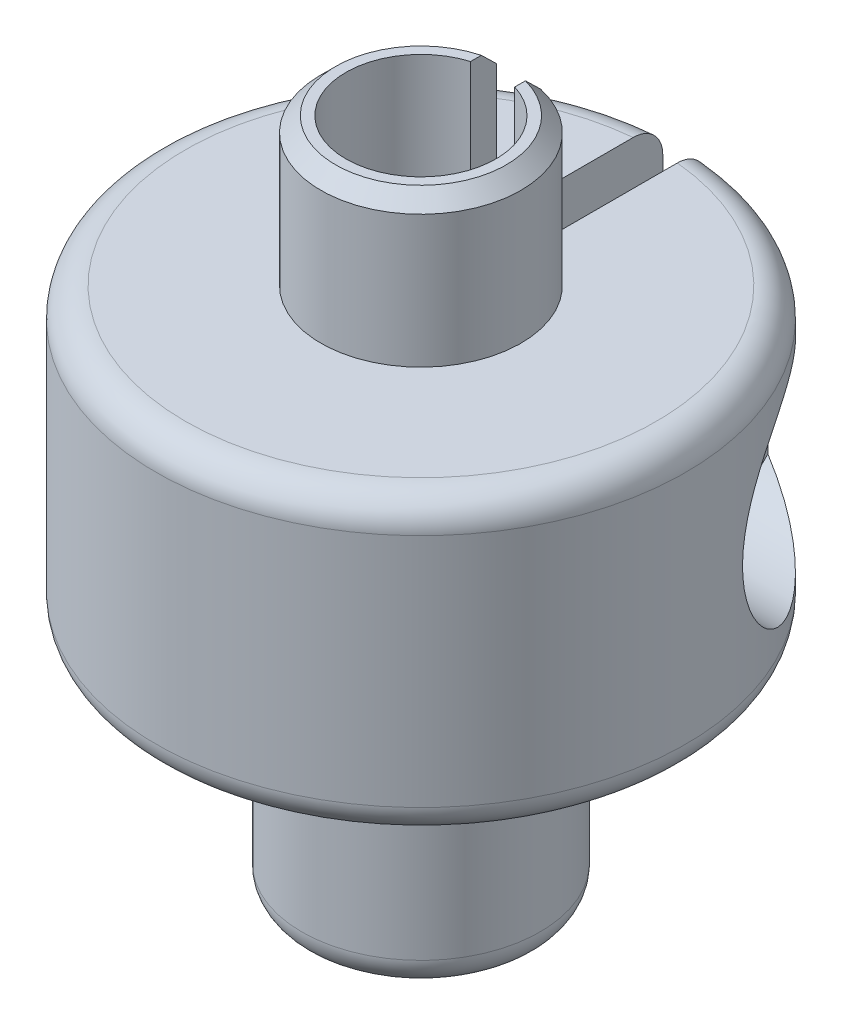
SolidWorks part; units mm, degrees
ref_plane "Front Plane" through (0, 0, 0) normal (0, 0, 1) x (1, 0, 0)
ref_plane "Top Plane" through (0, 0, 0) normal (0, 1, 0) x (1, 0, 0)
ref_plane "Right Plane" through (0, 0, 0) normal (1, 0, 0) x (0, 0, -1)
sketch "Sketch1" plane through (0, 0, 0) normal (0, 1, 0) x (1, 0, 0)
  circle A0 centre (0, 0) radius 4.05
  dimension "D1" = 8.1
extrude "Boss-Extrude1" add sketch "Sketch1" along normal blind 8
sketch "Sketch2" plane through (0, 8, 0) normal (0, 1, 0) x (1, 0, 0)
  circle A0 centre (0, 0) radius 9
  dimension "D1" = 18
extrude "Boss-Extrude2" add sketch "Sketch2" along normal blind 10
fillet "Fillet1" radius 1 3 edges at (0, 0, 4.05) (0, 8, 9) (0, 18, 9)
sketch "Sketch3" plane through (0, 18, 0) normal (0, 1, 0) x (1, 0, 0)
  circle A0 centre (0, 0) radius 2.55
  dimension "D1" = 5.1
extrude "Cut-Extrude1" cut sketch "Sketch3" against normal blind 10 contours A0
sketch "Sketch20" plane through (0, 18, 0) normal (0, 1, 0) x (1, 0, 0)
  line L1 (-0.75, 2.4372) -> (0.75, 2.4372)
  line L2 (-0.75, 2.4372) -> (-0.75, 8.9687)
  line L4 (0.75, 2.4372) -> (0.75, 8.9687)
  circle A0 centre (0, 0) radius 2.55 construction
  circle A1 centre (0, 0) radius 2.55 construction
  circle A2 centre (0, 0) radius 9 construction
  arc A3 (0.75, 8.9687) -> (-0.75, 8.9687) centre (0, 0) ccw
  dimension "D1" = 1.5
extrude "Cut-Extrude2" cut sketch "Sketch20" against normal up to surface (10 mm away) up to face at (0, 8, 8)
ref_plane "Plane2" through (10, 0, 0) normal (1, 0, 0) x (0, 0, -1)
sketch "Sketch32" plane through (10, 0, 0) normal (1, 0, 0) x (0, 0, -1)
  line L0 (8.9687, 9) -> (8.9687, 17) construction
  line L1 (8.9687, 9) -> (8.9687, 17) construction
  line L2 (2.4372, 8) -> (2.4372, 18) construction
  line L3 (2.4372, 8) -> (2.4372, 18) construction
  line L4 (2.4372, 13) -> (8.9687, 13) construction
  point P0 (5.703, 13)
  point P5 (8.9687, 13)
  point P17 (5.703, 13)
hole_wizard "M3 Clearance Hole1" positions "Sketch32" profile "Sketch26" hole size "M3" standard "ANSI Metric" end condition through all
sketch "Sketch26" plane through (10, 13, -5.703) normal (0, 1, 0) x (0, 0, -1)
  line L0 (0, 0) -> (0, 19)
  line L1 (0, 19) -> (1.7, 19)
  line L2 (1.7, 19) -> (1.7, 0)
  line L5 (1.7, 0) -> (0, 0)
  line L11 (0, -6.35) -> (0, 107.95) construction
  dimension "Thru Hole Dia." = 3.4
  dimension "Thru Hole Depth" = 19
sketch "Sketch28" plane through (10, 0, 0) normal (1, 0, 0) x (0, 0, -1)
  circle A0 centre (5.703, 13) radius 1.7 construction
  circle A1 centre (5.703, 13) radius 1.7 construction
  circle A2 centre (5.703, 13) radius 3.5
  dimension "D1" = 7
extrude "Cut-Extrude3" cut sketch "Sketch28" against normal blind 6.5
mirror "Mirror1" about plane through (0, 0, 0) normal (1, 0, 0) of "Cut-Extrude3"
sketch "Sketch29" plane through (0, 0, 0) normal (0, 0, 1) x (1, 0, 0)
  line L0 (-4.05, 8) -> (-4.05, 1) construction
  line L1 (4.05, 8) -> (-4.05, 8)
  line L2 (4.05, 8) -> (4.05, 7.5)
  line L3 (4.05, 7.5) -> (-4.05, 7.5)
  line L4 (-4.05, 8) -> (-4.05, 7.5)
  dimension "D1" = 0.5
extrude "Cut-Extrude7" cut sketch "Sketch29" against normal through all
fillet "Fillet2" radius 0.25 3 edges at (3.3, 8, 0) (-3.3, 8, 0) (0, 7.5, 0)
sketch "Sketch30" plane through (0, 18, 0) normal (0, 1, 0) x (1, 0, 0)
  line L0 (-0.75, 7.9648) -> (-0.75, 2.4372) construction
  line L1 (0.75, 2.4372) -> (0.75, 7.9648) construction
  line L2 (-0.75, 3.3162) -> (-0.75, 2.4372)
  line L3 (0.75, 2.4372) -> (0.75, 3.3162)
  arc A0 (-0.75, 2.4372) -> (0.75, 2.4372) centre (0, 0) ccw
  arc A1 (-0.75, 3.3162) -> (0.75, 3.3162) centre (0, 0) ccw
  dimension "D1" = 3.4
extrude "Boss-Extrude3" add sketch "Sketch30" along normal blind 5
chamfer "Chamfer1" distance 0.5 angle 45 1 edges at (0, 23, 3.4)
equation "\"1.5.00mm\"=6"
